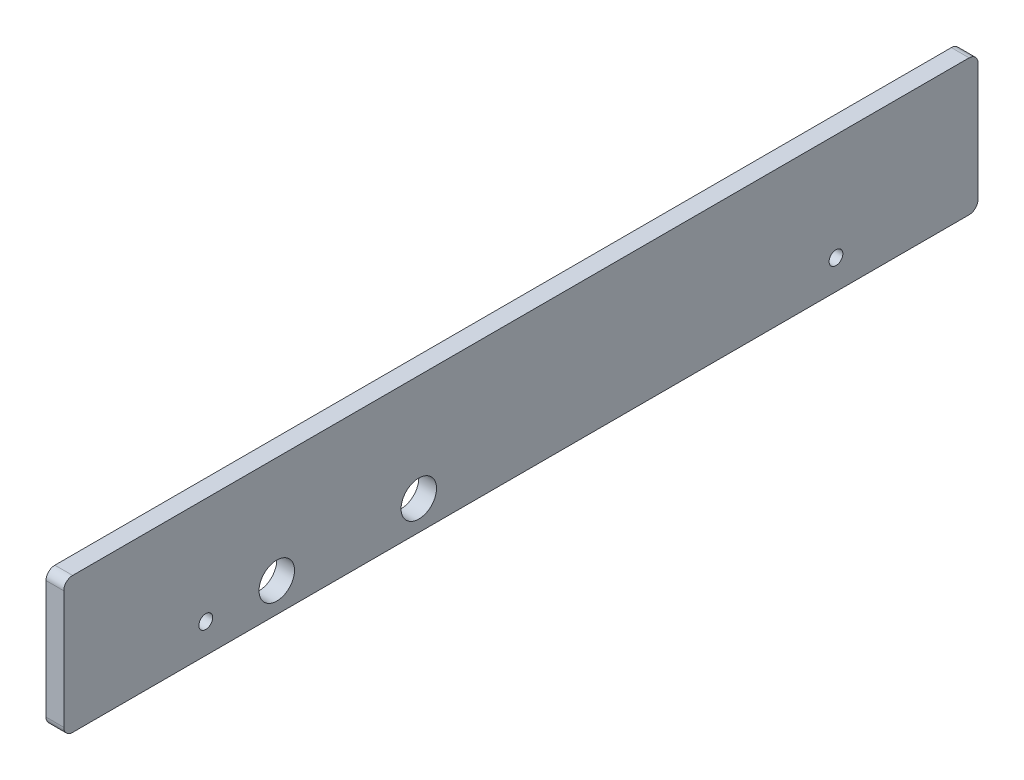
SolidWorks part; units mm, degrees
material "PE High Density"
ref_plane "Front Plane" through (0, 0, 0) normal (0, 0, 1) x (1, 0, 0)
ref_plane "Top Plane" through (0, 0, 0) normal (0, 1, 0) x (1, 0, 0)
ref_plane "Right Plane" through (0, 0, 0) normal (1, 0, 0) x (0, 0, -1)
sketch "Sketch1" plane through (0, 0, 0) normal (1, 0, 0) x (0, 0, -1)
  line L1 (0, 0) -> (327.025, 0)
  line L2 (0, 0) -> (0, 48.6359)
  line L3 (0, 48.6359) -> (327.025, 48.6359)
  line L4 (327.025, 0) -> (327.025, 48.6359)
  circle A0 centre (50.8, 10.5359) radius 2.4574
  circle A1 centre (276.225, 10.5359) radius 2.4575
  circle A2 centre (76.2, 10.5359) radius 6.35
  circle A3 centre (127, 10.5359) radius 6.35
  point P13 (0, 0)
  dimension "D3" = 4.9149
  dimension "D7" = 4.9149
  dimension "D10" = 12.7
  dimension "D1" = 48.6359
  dimension "D2" = 327.025
  dimension "D4" = 50.8
  dimension "D5" = 225.425
  dimension "D6" = 38.1
  dimension "D8" = 25.4
  dimension "D9" = 50.8
extrude "Boss-Extrude1" add sketch "Sketch1" along normal blind 6.35
fillet "Fillet1" radius 3.175 4 edges at (3.175, 48.6359, -327.025) (3.175, 0, -327.025) (3.175, 0, 0) (3.175, 48.6359, 0)
